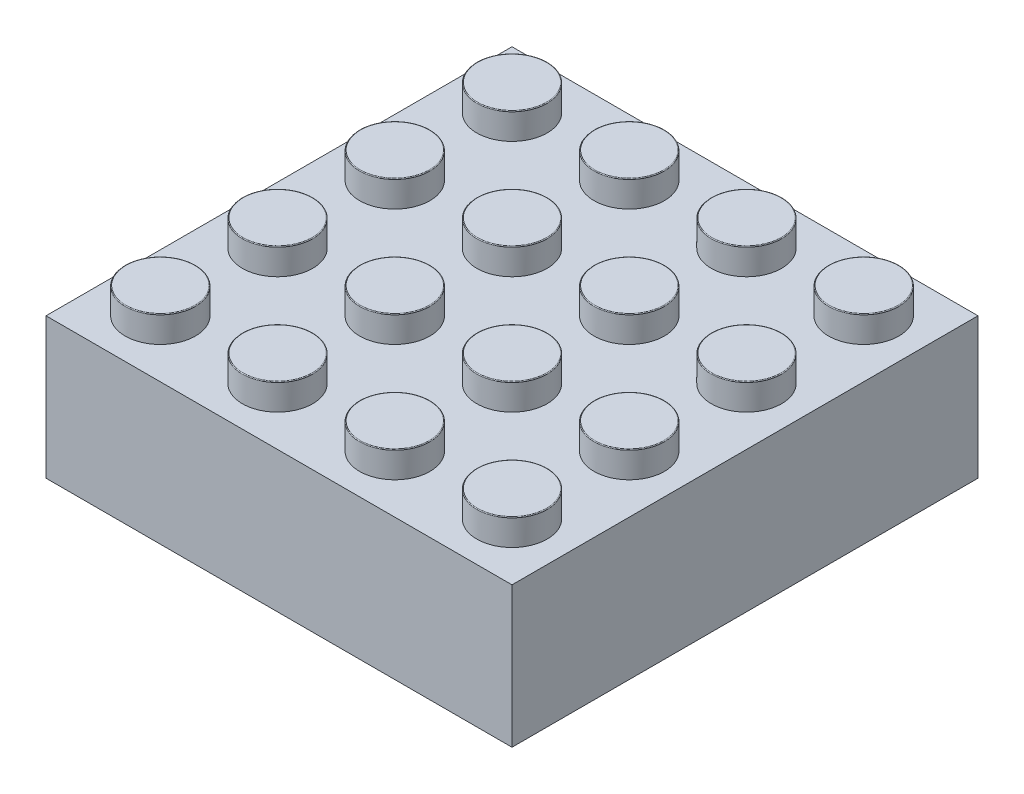
SolidWorks part; units mm, degrees
ref_plane "Front Plane" through (0, 0, 0) normal (0, 0, 1) x (1, 0, 0)
ref_plane "Top Plane" through (0, 0, 0) normal (0, 1, 0) x (1, 0, 0)
ref_plane "Right Plane" through (0, 0, 0) normal (1, 0, 0) x (0, 0, -1)
sketch "Sketch1" plane through (0, 0, 0) normal (0, 1, 0) x (1, 0, 0)
  line L1 (-15.9, -15.9) -> (15.9, -15.9)
  line L2 (-15.9, -15.9) -> (-15.9, 15.9)
  line L3 (-15.9, 15.9) -> (15.9, 15.9)
  line L4 (15.9, -15.9) -> (15.9, 15.9)
  line L5 (-15.9, -15.9) -> (15.9, 15.9) construction
  line L6 (-15.9, 15.9) -> (15.9, -15.9) construction
  point P0 (0, 0)
  dimension "D1" = 31.8
  dimension "D2" = 31.8
extrude "Boss-Extrude1" add sketch "Sketch1" along normal blind 9.6
sketch "Sketch2" plane through (0, 9.6, 0) normal (0, 1, 0) x (1, 0, 0)
  line L0 (-15.9, -15.9) -> (15.9, -15.9) construction
  line L1 (-15.9, 15.9) -> (-15.9, -15.9) construction
  circle A0 centre (-12, -12) radius 2.4
  dimension "D1" = 4.8
  dimension "D2" = 3.9
  dimension "D3" = 3.9
extrude "Boss-Extrude2" add sketch "Sketch2" along normal blind 1.8
pattern_linear "LPattern1" count 4 spacing 8 along (0, 0, -1) of "Boss-Extrude2"
pattern_linear "LPattern2" count 4 spacing 8 along (1, 0, 0) of "LPattern1"
fillet "Fillet1" radius 0.05 16 edges at (-12, 11.4, 14.4) (12, 11.4, 14.4) (-4, 11.4, -9.6) (4, 11.4, -9.6) (12, 11.4, -9.6) (12, 11.4, -1.6) (4, 11.4, -1.6) (-4, 11.4, -1.6) (4, 11.4, 14.4) (-4, 11.4, 14.4) (-4, 11.4, 6.4) (4, 11.4, 6.4) (12, 11.4, 6.4) (-12, 11.4, -9.6) (-12, 11.4, -1.6) (-12, 11.4, 6.4)
sketch "Sketch3" plane through (0, 0, 0) normal (0, -1, 0) x (-1, 0, 0)
  line L0 (15.9, 15.9) -> (15.9, -15.9) construction
  line L1 (-14.7, 14.7) -> (14.7, 14.7)
  line L2 (-14.7, 14.7) -> (-14.7, -14.7)
  line L3 (-14.7, -14.7) -> (14.7, -14.7)
  line L4 (14.7, 14.7) -> (14.7, -14.7)
  line L5 (-14.7, 14.7) -> (14.7, -14.7) construction
  line L6 (-14.7, -14.7) -> (14.7, 14.7) construction
  line L7 (15.9, -15.9) -> (-15.9, -15.9) construction
  point P0 (0, 0)
  dimension "D1" = 1.2
  dimension "D2" = 1.2
extrude "Cut-Extrude1" cut sketch "Sketch3" against normal blind 6.8
sketch "Sketch4" plane through (0, 6.8, 0) normal (0, -1, 0) x (-1, 0, 0)
  circle A0 centre (-8, 8) radius 3.2125
  circle A2 centre (-12, 4) radius 2.4 construction
  circle A3 centre (-12, 12) radius 2.4 construction
  point P6 (-12, 4)
  dimension "D1" = 6.425
  dimension "D3" = 4
  dimension "D2" = 4
extrude "Boss-Extrude3" add sketch "Sketch4" along normal up to surface (6.8 mm away) up to face at (0, 0, 0)
sketch "Sketch5" plane through (0, 0, 0) normal (0, -1, 0) x (-1, 0, 0)
  circle A0 centre (-8, 8) radius 2.25
  circle A1 centre (-8, 8) radius 3.2125 construction
  dimension "D1" = 4.5
extrude "Cut-Extrude2" cut sketch "Sketch5" against normal up to surface (6.8 mm away) up to face at (8, 6.8, -11.2125)
pattern_linear "LPattern3" count 3 spacing 8 along (-1, 0, 0) of "Cut-Extrude2", "Boss-Extrude3"
pattern_linear "LPattern4" count 3 spacing 8 along (0, 0, 1) of "LPattern3"
ref_axis "Axis1" through (0, 0, 0) along (0, 1, 0)
sketch "Sketch6" plane through (0, 0, 0) normal (0, -1, 0) x (-1, 0, 0)
  line L0 (14.7, -14.7) -> (14.7, 14.7) construction
  line L1 (14.7, -12.3) -> (14.4, -12.3)
  line L2 (14.7, -12.3) -> (14.7, -11.7)
  line L3 (14.7, -11.7) -> (14.4, -11.7)
  line L4 (14.4, -12.3) -> (14.4, -11.7)
  line L5 (14.7, -14.7) -> (14.7, 14.7) construction
  line L6 (14.7, -4.3) -> (14.4, -4.3)
  line L7 (14.7, -4.3) -> (14.7, -3.7)
  line L8 (14.7, -3.7) -> (14.4, -3.7)
  line L9 (14.4, -4.3) -> (14.4, -3.7)
  line L10 (15.9, -15.9) -> (-15.9, -15.9) construction
  line L11 (14.7, 3.7) -> (14.4, 3.7)
  line L12 (14.7, 3.7) -> (14.7, 4.3)
  line L13 (14.7, 4.3) -> (14.4, 4.3)
  line L14 (14.4, 3.7) -> (14.4, 4.3)
  line L15 (14.7, 11.7) -> (14.4, 11.7)
  line L16 (14.7, 11.7) -> (14.7, 12.3)
  line L17 (14.7, 12.3) -> (14.4, 12.3)
  line L18 (14.4, 11.7) -> (14.4, 12.3)
  line L19 (-15.9, 15.9) -> (15.9, 15.9) construction
  point P20 (14.7, -12)
  point P23 (14.7, 12)
  point P26 (0, 0)
  dimension "D1" = 0.3
  dimension "D2" = 0.6
  dimension "D3" = 0.6
  dimension "D4" = 0.6
  dimension "D5" = 0.6
  dimension "D6" = 3.9
  dimension "D9" = 3.9
  dimension "D7" = 8
  dimension "D8" = 8
extrude "Boss-Extrude4" add sketch "Sketch6" against normal up to surface (6.8 mm away) up to face at (-8, 6.8, 4.7875)
pattern_circular "CirPattern1" count 4 over 360 about axis through (0, 0, 0) along (0, 1, 0) of "Boss-Extrude4"
equation "\"D2@Sketch1\"=\"D1@Sketch1\""
equation "\"D3@Sketch2\"=\"D2@Sketch2\""
equation "\"D2@Sketch3\"=\"D1@Sketch3\""
equation "\"D3@Sketch6\"=\"D2@Sketch6\""
equation "\"D4@Sketch6\"=\"D3@Sketch6\""
equation "\"D5@Sketch6\"=\"D4@Sketch6\""
